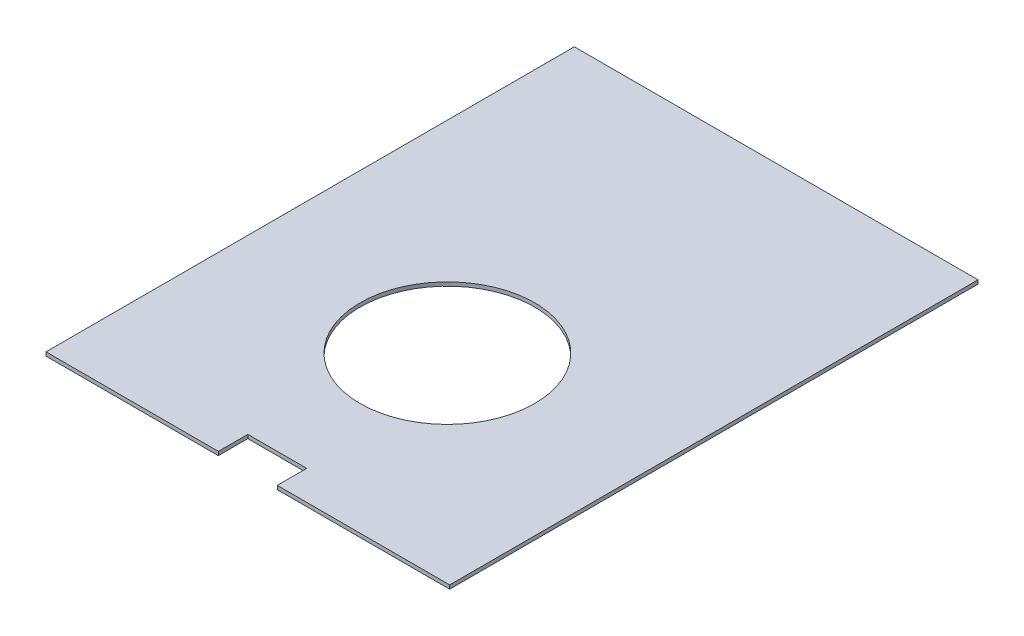
SolidWorks part; units mm, degrees
ref_plane "Front Plane" through (0, 0, 0) normal (0, 0, 1) x (1, 0, 0)
ref_plane "Top Plane" through (0, 0, 0) normal (0, 1, 0) x (1, 0, 0)
ref_plane "Right Plane" through (0, 0, 0) normal (1, 0, 0) x (0, 0, -1)
sketch "Sketch4" plane through (0, 0, 0) normal (0, 1, 0) x (1, 0, 0)
  line L1 (-190.5, -254) -> (190.5, -254)
  line L2 (-190.5, -254) -> (-190.5, 254)
  line L3 (-190.5, 254) -> (190.5, 254)
  line L4 (190.5, -254) -> (190.5, 254)
  line L5 (-190.5, -254) -> (190.5, 254) construction
  line L6 (-190.5, 254) -> (190.5, -254) construction
  point P0 (0, 0)
extrude "Boss-Extrude1" add sketch "Sketch4" along normal blind 3.81
sketch "Sketch7" plane through (0, 3.81, 0) normal (0, 1, 0) x (1, 0, 0)
  line L1 (-205.5, -269) -> (205.5, -269)
  line L2 (-205.5, -269) -> (-205.5, 269)
  line L3 (-205.5, 269) -> (205.5, 269)
  line L4 (190.5, -254) -> (190.5, 254)
  line L5 (190.5, 254) -> (-190.5, 254)
  line L6 (-190.5, 254) -> (-190.5, -254)
  line L7 (-190.5, -254) -> (190.5, -254)
  line L8 (190.5, -254) -> (190.5, 254)
  line L9 (190.5, 254) -> (-190.5, 254)
  line L10 (-190.5, 254) -> (-190.5, -254)
  line L11 (-190.5, -254) -> (190.5, -254)
  line L12 (205.5, -269) -> (205.5, 269)
  line L13 (-205.5, -269) -> (205.5, 269) construction
  line L14 (-205.5, 269) -> (205.5, -269) construction
  point P2 (0, 0)
  dimension "D2" = 15
  dimension "D3" = 15
  dimension "D1" = 0
extrude "Boss-Extrude2" add sketch "Sketch7" against normal up to surface (3.81 mm away) up to face at (0, 0, 0)
sketch "Sketch5" plane through (0, 3.81, 0) normal (0, 1, 0) x (1, 0, 0)
  line L0 (0, -269) -> (0, -65.8) construction
  line L2 (-205.5, -269) -> (205.5, -269) construction
  circle A0 centre (0, -65.8) radius 88.9
  dimension "D1" = 177.8
  dimension "D2" = 203.2
extrude "Cut-Extrude1" cut sketch "Sketch5" against normal through all
sketch "Sketch6" plane through (0, 3.81, 0) normal (0, 1, 0) x (1, 0, 0)
  line L1 (0, 0) -> (0, -239) construction
  line L2 (-30, -269) -> (30, -269)
  line L3 (-30, -269) -> (-30, -239)
  line L4 (-30, -239) -> (30, -239)
  line L5 (30, -269) -> (30, -239)
  line L6 (-205.5, -269) -> (205.5, -269) construction
  dimension "D1" = 60
  dimension "D2" = 30
extrude "Cut-Extrude2" cut sketch "Sketch6" against normal through all
